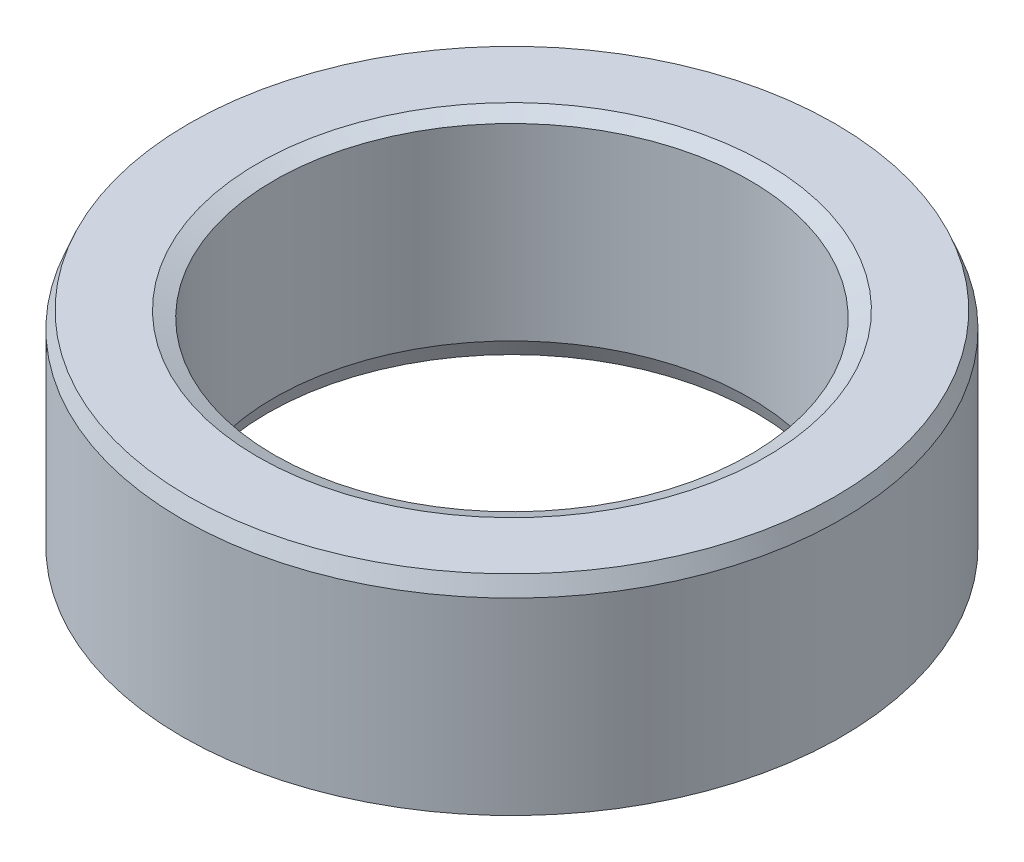
SolidWorks part; units mm, degrees
ref_plane "Front Plane" through (0, 0, 0) normal (0, 0, 1) x (1, 0, 0)
ref_plane "Top Plane" through (0, 0, 0) normal (0, 1, 0) x (1, 0, 0)
ref_plane "Right Plane" through (0, 0, 0) normal (1, 0, 0) x (0, 0, -1)
sketch "Sketch1" plane through (0, 0, 0) normal (0, 1, 0) x (1, 0, 0)
  circle A0 centre (0, 0) radius 57.5
  dimension "SLEEVE_OD" = 115
extrude "Boss-Extrude1" add sketch "Sketch1" along normal blind 36.8528
sketch "Sketch2" plane through (0, 0, 0) normal (0, 1, 0) x (1, 0, 0)
  circle A0 centre (0, 0) radius 41.4837
  dimension "BORE_D" = 82.9674
extrude "Cut-Extrude1" cut sketch "Sketch2" along normal through all
chamfer "Chamfer1" distance 2.8646 angle 21.619 4 edges at (0, 36.8528, 41.4837) (0, 0, 41.4837) (0, 0, 57.5) (0, 36.8528, 57.5) first distance on face at (0, 36.8528, 41.4837) first distance on face at (0, 0, 41.4837) first distance on face at (0, 36.8528, 57.5)
